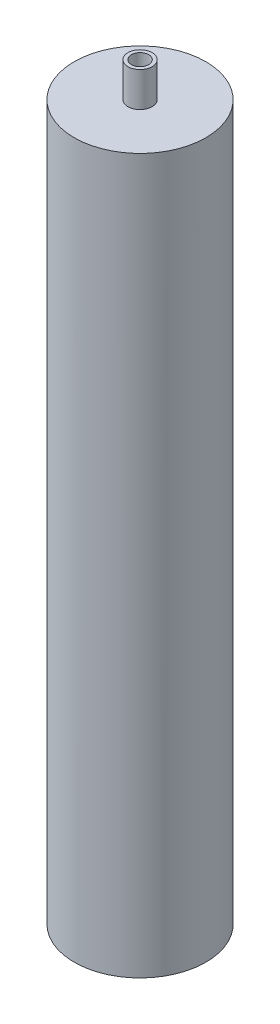
SolidWorks part; units mm, degrees
material "ABS"
ref_plane "前视基准面" through (0, 0, 0) normal (0, 0, 1) x (1, 0, 0)
ref_plane "上视基准面" through (0, 0, 0) normal (0, 1, 0) x (1, 0, 0)
ref_plane "右视基准面" through (0, 0, 0) normal (1, 0, 0) x (0, 0, -1)
sketch "草图1" plane through (0, 0, 0) normal (0, 1, 0) x (1, 0, 0)
  circle A0 centre (0, 0) radius 19
  circle A1 centre (0, 0) radius 18
  dimension "D1" = 38
  dimension "D2" = 36
extrude "凸台-拉伸1" add sketch "草图1" along normal blind 150
sketch "草图2" plane through (0, 150, 0) normal (0, 1, 0) x (1, 0, 0)
  circle A0 centre (0, 0) radius 19
  circle A2 centre (0, 0) radius 10 construction
  circle A3 centre (0, 10) radius 2
  circle A4 centre (10, 0) radius 2
  circle A5 centre (-10, 0) radius 2
  circle A6 centre (0, -10) radius 2
  circle A7 centre (0, 0) radius 2.5
  dimension "D1" = 38
  dimension "D2" = 20
  dimension "D3" = 4
  dimension "D4" = 4
  dimension "D5" = 4
  dimension "D6" = 4
  dimension "D7" = 5
extrude "凸台-拉伸2" add sketch "草图2" along normal blind 2
sketch "草图3" plane through (0, 152, 0) normal (0, 1, 0) x (1, 0, 0)
  circle A0 centre (0, 0) radius 19
  circle A1 centre (0, 0) radius 18
  dimension "D1" = 38
  dimension "D2" = 36
extrude "凸台-拉伸3" add sketch "草图3" along normal blind 50
sketch "草图4" plane through (0, 202, 0) normal (0, 1, 0) x (1, 0, 0)
  circle A0 centre (0, 0) radius 19
  circle A1 centre (0, 0) radius 2.5
  dimension "D1" = 38
  dimension "D2" = 5
extrude "凸台-拉伸4" add sketch "草图4" along normal blind 2
sketch "草图5" plane through (0, 204, 0) normal (0, 1, 0) x (1, 0, 0)
  circle A0 centre (0, 0) radius 2.5
  circle A1 centre (0, 0) radius 3.5
  dimension "D1" = 5
  dimension "D2" = 7
extrude "凸台-拉伸5" add sketch "草图5" along normal blind 10
sketch "草图6" plane through (0, 0, 0) normal (0, -1, 0) x (1, 0, 0)
  circle A0 centre (0, 0) radius 19
  circle A1 centre (0, 0) radius 12.5
  dimension "D1" = 38
  dimension "D2" = 25
extrude "凸台-拉伸6" add sketch "草图6" along normal blind 2
